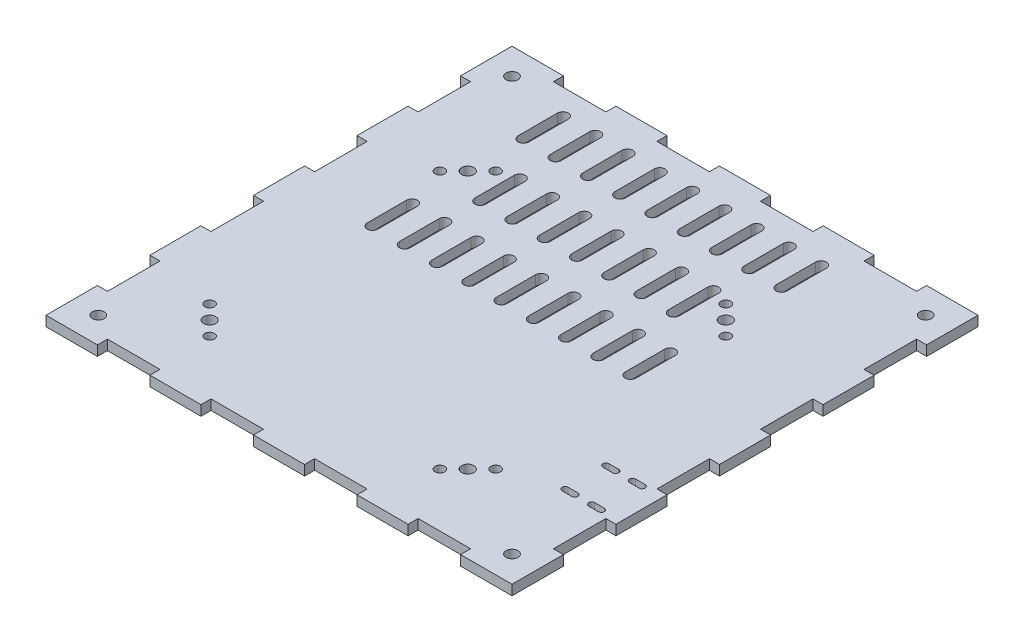
SolidWorks part; units mm, degrees
material "Acrylic (Medium-high impact)"
ref_plane "Front Plane" through (0, 0, 0) normal (0, 0, 1) x (1, 0, 0)
ref_plane "Top Plane" through (0, 0, 0) normal (0, 1, 0) x (1, 0, 0)
ref_plane "Right Plane" through (0, 0, 0) normal (1, 0, 0) x (0, 0, -1)
sketch "Board refrence" plane through (0, 0, 0) normal (0, 1, 0) x (1, 0, 0)
  line L0 (42.5, -17.26) -> (47.5, -17.26)
  line L1 (-40, -40) -> (40, -40)
  line L2 (-40, -40) -> (-40, 40)
  line L3 (-40, 40) -> (40, 40)
  line L4 (40, -40) -> (40, 40)
  line L5 (-40, -40) -> (40, 40) construction
  line L6 (-40, 40) -> (40, -40) construction
  line L7 (-50.8, 46.35) -> (50.8, 46.35)
  line L8 (-50.8, 46.35) -> (-50.8, 40)
  line L9 (-50.8, 40) -> (50.8, 40)
  line L10 (50.8, 46.35) -> (50.8, 40)
  line L11 (42.5, -25.26) -> (47.5, -25.26)
  line L12 (45, -25.26) -> (45, -17.26) construction
  circle A0 centre (-36, 36) radius 1.6
  circle A1 centre (-36, -36) radius 1.6
  circle A2 centre (36, -36) radius 1.6
  circle A3 centre (36, 36) radius 1.6
  point P0 (0, 0)
  point P14 (0, 40)
  point P15 (0, 40)
  point P26 (45, -21.26)
  dimension "D4" = 3.2
  dimension "D1" = 80
  dimension "D2" = 80
  dimension "D3" = 4
  dimension "D5" = 6.35
  dimension "D6" = 101.6
  dimension "D7" = 18.74
  dimension "D8" = 8
  dimension "D9" = 5
  dimension "D10" = 5
sketch "Sketch2" plane through (0, 0, 0) normal (0, 1, 0) x (1, 0, 0)
  line L0 (-40, -40) -> (-40, 40) construction
  line L1 (-56.8, 69.15) -> (66.8, 69.15) construction
  line L2 (-56.8, 69.15) -> (-56.8, -54.45) construction
  line L3 (-56.8, -54.45) -> (66.8, -54.45) construction
  line L4 (66.8, 69.15) -> (66.8, -54.45) construction
  line L6 (40, -40) -> (40, 40) construction
  line L7 (-50.8, 46.35) -> (50.8, 46.35) construction
  line L8 (-60, 72.35) -> (-60, -57.65)
  line L9 (-60, -57.65) -> (70, -57.65)
  line L10 (70, 72.35) -> (70, -57.65)
  line L11 (-60, 72.35) -> (70, 72.35)
  circle A0 centre (-36, 36) radius 1.7
  circle A1 centre (-36, -36) radius 1.7
  circle A2 centre (36, -36) radius 1.7
  circle A3 centre (36, 36) radius 1.7
  point P16 (0, 0)
  dimension "D1" = 3.4
  dimension "D2" = 20
  dimension "D3" = 26
  dimension "D4" = 30
  dimension "D6" = 130
  dimension "D7" = 130
  dimension "D5" = 3.2
extrude "Boss-Extrude1" add sketch "Sketch2" along normal blind 2.8
sketch "Sketch5" plane through (0, 2.8, 0) normal (0, 1, 0) x (1, 0, 0)
  line L0 (32.1109, 39.8891) -> (39.8891, 32.1109) construction
  line L1 (70, -57.65) -> (70, 72.35) construction
  circle A0 centre (39.8891, 32.1109) radius 1.35
  circle A1 centre (32.1109, 39.8891) radius 1.35
  circle A2 centre (32.1109, -39.8891) radius 1.35
  circle A3 centre (39.8891, -32.1109) radius 1.35
  circle A4 centre (-39.8891, -32.1109) radius 1.35
  circle A5 centre (-32.1109, -39.8891) radius 1.35
  circle A6 centre (-32.1109, 39.8891) radius 1.35
  circle A7 centre (-39.8891, 32.1109) radius 1.35
  point P4 (36, 36)
  point P23 (0, 0)
  dimension "D3" = 2.7
  dimension "D1" = 45
  dimension "D2" = 11
extrude "Cut-Extrude2" cut sketch "Sketch5" against normal up to next
sketch "Sketch4" plane through (0, 2.8, 0) normal (0, 1, 0) x (1, 0, 0)
  line L0 (70, 57.9056) -> (70, 43.4611)
  line L1 (70, -57.65) -> (70, 72.35) construction
  line L2 (70, 14.5722) -> (67.2, 14.5722)
  line L3 (67.2, 14.5722) -> (67.2, 29.0167)
  line L4 (67.2, 29.0167) -> (70, 29.0167)
  line L5 (70, 29.0167) -> (70, 14.5722)
  line L6 (70, -14.3167) -> (67.2, -14.3167)
  line L7 (67.2, -14.3167) -> (67.2, 0.1278)
  line L8 (67.2, 0.1278) -> (70, 0.1278)
  line L9 (70, 0.1278) -> (70, -14.3167)
  line L10 (70, 43.4611) -> (67.2, 43.4611)
  line L11 (67.2, 43.4611) -> (67.2, 57.9056)
  line L12 (67.2, 57.9056) -> (70, 57.9056)
  line L13 (70, -43.2056) -> (67.2, -43.2056)
  line L14 (67.2, -43.2056) -> (67.2, -28.7611)
  line L15 (67.2, -28.7611) -> (70, -28.7611)
  line L16 (70, -28.7611) -> (70, -43.2056)
  line L17 (70, 43.4611) -> (70, 14.5722) construction
  line L18 (67.2, -43.2056) -> (67.2, -57.65) construction
  line L19 (-60, -57.65) -> (70, -57.65) construction
  line L20 (67.2, -28.7611) -> (67.2, -14.3167) construction
  line L21 (70, 72.35) -> (-60, 72.35) construction
  line L42 (-60, 72.35) -> (70, -57.65) construction
  line L66 (-45.5556, -57.65) -> (-45.5556, -54.85)
  line L67 (-45.5556, -54.85) -> (-31.1111, -54.85)
  line L68 (-31.1111, -54.85) -> (-31.1111, -57.65)
  line L91 (67.2, 0.1278) -> (67.2, 14.5722) construction
  line L92 (67.2, 29.0167) -> (67.2, 43.4611) construction
  line L93 (67.2, 57.9056) -> (67.2, 72.35) construction
  line L94 (-31.1111, -57.65) -> (-45.5556, -57.65)
  line L95 (-16.6667, -57.65) -> (-16.6667, -54.85)
  line L96 (-16.6667, -54.85) -> (-2.2222, -54.85)
  line L97 (-2.2222, -54.85) -> (-2.2222, -57.65)
  line L103 (-2.2222, -57.65) -> (-16.6667, -57.65)
  line L108 (12.2222, -57.65) -> (12.2222, -54.85)
  line L113 (12.2222, -54.85) -> (26.6667, -54.85)
  line L118 (26.6667, -54.85) -> (26.6667, -57.65)
  line L119 (26.6667, -57.65) -> (12.2222, -57.65)
  line L120 (55.5556, -57.65) -> (41.1111, -57.65)
  line L121 (41.1111, -57.65) -> (41.1111, -54.85)
  line L125 (41.1111, -54.85) -> (55.5556, -54.85)
  line L126 (55.5556, -54.85) -> (55.5556, -57.65)
  line L127 (-60, 57.9056) -> (-57.2, 57.9056)
  line L128 (-57.2, 57.9056) -> (-57.2, 43.4611)
  line L129 (-57.2, 43.4611) -> (-60, 43.4611)
  line L130 (-60, 43.4611) -> (-60, 57.9056)
  line L131 (-60, 29.0167) -> (-57.2, 29.0167)
  line L132 (-57.2, 29.0167) -> (-57.2, 14.5722)
  line L133 (-57.2, 14.5722) -> (-60, 14.5722)
  line L134 (-60, 14.5722) -> (-60, 29.0167)
  line L135 (-60, 0.1278) -> (-57.2, 0.1278)
  line L136 (-57.2, 0.1278) -> (-57.2, -14.3167)
  line L137 (-57.2, -14.3167) -> (-60, -14.3167)
  line L138 (-60, -14.3167) -> (-60, 0.1278)
  line L139 (-60, -43.2056) -> (-60, -28.7611)
  line L140 (-60, -28.7611) -> (-57.2, -28.7611)
  line L141 (-57.2, -28.7611) -> (-57.2, -43.2056)
  line L142 (-57.2, -43.2056) -> (-60, -43.2056)
  line L143 (55.5556, 72.35) -> (55.5556, 69.55)
  line L144 (55.5556, 69.55) -> (41.1111, 69.55)
  line L145 (41.1111, 69.55) -> (41.1111, 72.35)
  line L146 (41.1111, 72.35) -> (55.5556, 72.35)
  line L147 (26.6667, 72.35) -> (26.6667, 69.55)
  line L148 (26.6667, 69.55) -> (12.2222, 69.55)
  line L149 (12.2222, 69.55) -> (12.2222, 72.35)
  line L150 (12.2222, 72.35) -> (26.6667, 72.35)
  line L151 (-2.2222, 72.35) -> (-2.2222, 69.55)
  line L152 (-2.2222, 69.55) -> (-16.6667, 69.55)
  line L153 (-16.6667, 69.55) -> (-16.6667, 72.35)
  line L154 (-16.6667, 72.35) -> (-2.2222, 72.35)
  line L155 (-45.5556, 72.35) -> (-31.1111, 72.35)
  line L156 (-31.1111, 72.35) -> (-31.1111, 69.55)
  line L157 (-31.1111, 69.55) -> (-45.5556, 69.55)
  line L158 (-45.5556, 69.55) -> (-45.5556, 72.35)
  point P27 (5, 7.35)
  point P81 (5, 7.35)
  dimension "D4" = 2.8
  dimension "D1" = 4
  dimension "D2" = 4
extrude "Cut tabs" cut sketch "Sketch4" against normal through all
sketch "Pad reference" plane through (0, 2.8, 0) normal (0, 1, 0) x (1, 0, 0)
  line L2 (-60, -57.65) -> (-45.5556, -57.65) construction
  line L3 (55, 57.35) -> (-45, 57.35) construction
  line L4 (55, 57.35) -> (55, -42.65) construction
  line L5 (55, -42.65) -> (-45, -42.65) construction
  line L7 (-45, 57.35) -> (-45, -42.65) construction
  line L151 (70, -57.65) -> (70, -43.2056) construction
  line L152 (70, 72.35) -> (55.5556, 72.35) construction
  circle A0 centre (-45, 57.35) radius 4
  circle A1 centre (55, 57.35) radius 4
  circle A2 centre (55, -42.65) radius 4
  circle A3 centre (-45, -42.65) radius 4
  point P6 (0, 0)
  dimension "D1" = 8
  dimension "D3" = 15
  dimension "D4" = 15
  dimension "D2" = 15
sketch "Sketch6" plane through (0, 2.8, 0) normal (0, 1, 0) x (1, 0, 0)
  line L0 (64.5, -27.2389) -> (61.8, -27.2389) construction
  line L1 (64.5, -28.0889) -> (61.8, -28.0889)
  line L2 (64.5, -26.3889) -> (61.8, -26.3889)
  line L3 (57.1, -27.2389) -> (54.4, -27.2389) construction
  line L4 (57.1, -28.0889) -> (54.4, -28.0889)
  line L5 (57.1, -26.3889) -> (54.4, -26.3889)
  line L6 (72.5, -21.5389) -> (-49927.5, -21.5389) construction
  line L7 (70, -28.7611) -> (70, -14.3167) construction
  line L8 (57.1, -15.8389) -> (54.4, -15.8389) construction
  line L9 (57.1, -14.9889) -> (54.4, -14.9889)
  line L10 (57.1, -16.6889) -> (54.4, -16.6889)
  line L11 (64.5, -15.8389) -> (61.8, -15.8389) construction
  line L12 (64.5, -14.9889) -> (61.8, -14.9889)
  line L13 (64.5, -16.6889) -> (61.8, -16.6889)
  arc A0 (64.5, -28.0889) -> (64.5, -26.3889) centre (64.5, -27.2389) ccw
  arc A1 (61.8, -26.3889) -> (61.8, -28.0889) centre (61.8, -27.2389) ccw
  arc A2 (57.1, -28.0889) -> (57.1, -26.3889) centre (57.1, -27.2389) ccw
  arc A3 (54.4, -26.3889) -> (54.4, -28.0889) centre (54.4, -27.2389) ccw
  arc A4 (57.1, -14.9889) -> (57.1, -16.6889) centre (57.1, -15.8389) cw
  arc A5 (54.4, -16.6889) -> (54.4, -14.9889) centre (54.4, -15.8389) cw
  arc A6 (64.5, -14.9889) -> (64.5, -16.6889) centre (64.5, -15.8389) cw
  arc A7 (61.8, -16.6889) -> (61.8, -14.9889) centre (61.8, -15.8389) cw
  point P2 (63.15, -27.2389)
  point P7 (55.75, -27.2389)
  point P18 (70, -21.5389)
  point P21 (55.75, -15.8389)
  point P28 (63.15, -15.8389)
  dimension "D3" = 3
  dimension "D1" = 4.4
  dimension "D2" = 1.7
  dimension "D4" = 4.85
  dimension "D5" = 5.5
extrude "Power cord slots" cut sketch "Sketch6" against normal up to next
sketch "Sketch7" plane through (0, 2.8, 0) normal (0, 1, 0) x (1, 0, 0)
  line L0 (-36, 62.55) -> (-36, 51.55) construction
  line L1 (-34.5, 62.55) -> (-34.5, 51.55)
  line L2 (-37.5, 62.55) -> (-37.5, 51.55)
  line L3 (-45.5556, 69.55) -> (-31.1111, 69.55) construction
  line L4 (-37.5, 20.45) -> (-37.5, 9.45)
  line L5 (-28.5, 62.55) -> (-28.5, 51.55)
  line L6 (-25.5, 62.55) -> (-25.5, 51.55)
  line L7 (-27, 62.55) -> (-27, 51.55) construction
  line L8 (-19.5, 62.55) -> (-19.5, 51.55)
  line L9 (-16.5, 62.55) -> (-16.5, 51.55)
  line L10 (-18, 62.55) -> (-18, 51.55) construction
  line L11 (-10.5, 62.55) -> (-10.5, 51.55)
  line L12 (-7.5, 62.55) -> (-7.5, 51.55)
  line L13 (-9, 62.55) -> (-9, 51.55) construction
  line L14 (-1.5, 62.55) -> (-1.5, 51.55)
  line L15 (1.5, 62.55) -> (1.5, 51.55)
  line L16 (0, 62.55) -> (0, 51.55) construction
  line L17 (7.5, 62.55) -> (7.5, 51.55)
  line L18 (10.5, 62.55) -> (10.5, 51.55)
  line L19 (9, 62.55) -> (9, 51.55) construction
  line L20 (16.5, 62.55) -> (16.5, 51.55)
  line L21 (19.5, 62.55) -> (19.5, 51.55)
  line L22 (18, 62.55) -> (18, 51.55) construction
  line L23 (25.5, 62.55) -> (25.5, 51.55)
  line L24 (28.5, 62.55) -> (28.5, 51.55)
  line L25 (27, 62.55) -> (27, 51.55) construction
  line L26 (34.5, 62.55) -> (34.5, 51.55)
  line L27 (37.5, 62.55) -> (37.5, 51.55)
  line L28 (36, 62.55) -> (36, 51.55) construction
  line L32 (-36, 36) -> (-36, 51.55) construction
  line L33 (-36, 36) -> (-36, 20.45) construction
  line L34 (-34.5, 20.45) -> (-34.5, 9.45)
  line L37 (-28.5, 41.5) -> (-28.5, 30.5)
  line L38 (-25.5, 41.5) -> (-25.5, 30.5)
  line L39 (-27, 41.5) -> (-27, 30.5) construction
  line L40 (-19.5, 41.5) -> (-19.5, 30.5)
  line L41 (-16.5, 41.5) -> (-16.5, 30.5)
  line L42 (-18, 41.5) -> (-18, 30.5) construction
  line L43 (-10.5, 41.5) -> (-10.5, 30.5)
  line L44 (-7.5, 41.5) -> (-7.5, 30.5)
  line L45 (-9, 41.5) -> (-9, 30.5) construction
  line L46 (-1.5, 41.5) -> (-1.5, 30.5)
  line L47 (1.5, 41.5) -> (1.5, 30.5)
  line L48 (0, 41.5) -> (0, 30.5) construction
  line L49 (7.5, 41.5) -> (7.5, 30.5)
  line L50 (10.5, 41.5) -> (10.5, 30.5)
  line L51 (9, 41.5) -> (9, 30.5) construction
  line L52 (16.5, 41.5) -> (16.5, 30.5)
  line L53 (19.5, 41.5) -> (19.5, 30.5)
  line L54 (18, 41.5) -> (18, 30.5) construction
  line L55 (25.5, 41.5) -> (25.5, 30.5)
  line L56 (28.5, 41.5) -> (28.5, 30.5)
  line L57 (27, 41.5) -> (27, 30.5) construction
  line L63 (-36, 20.45) -> (-36, 9.45) construction
  line L64 (-28.5, 20.45) -> (-28.5, 9.45)
  line L65 (-25.5, 20.45) -> (-25.5, 9.45)
  line L66 (-27, 20.45) -> (-27, 9.45) construction
  line L67 (-19.5, 20.45) -> (-19.5, 9.45)
  line L68 (-16.5, 20.45) -> (-16.5, 9.45)
  line L69 (-18, 20.45) -> (-18, 9.45) construction
  line L70 (-10.5, 20.45) -> (-10.5, 9.45)
  line L71 (-7.5, 20.45) -> (-7.5, 9.45)
  line L72 (-9, 20.45) -> (-9, 9.45) construction
  line L73 (-1.5, 20.45) -> (-1.5, 9.45)
  line L74 (1.5, 20.45) -> (1.5, 9.45)
  line L75 (0, 20.45) -> (0, 9.45) construction
  line L76 (7.5, 20.45) -> (7.5, 9.45)
  line L77 (10.5, 20.45) -> (10.5, 9.45)
  line L78 (9, 20.45) -> (9, 9.45) construction
  line L79 (16.5, 20.45) -> (16.5, 9.45)
  line L80 (19.5, 20.45) -> (19.5, 9.45)
  line L81 (18, 20.45) -> (18, 9.45) construction
  line L82 (25.5, 20.45) -> (25.5, 9.45)
  line L83 (28.5, 20.45) -> (28.5, 9.45)
  line L84 (27, 20.45) -> (27, 9.45) construction
  line L85 (34.5, 20.45) -> (34.5, 9.45)
  line L86 (37.5, 20.45) -> (37.5, 9.45)
  line L87 (36, 20.45) -> (36, 9.45) construction
  line L88 (34.5, 41.5) -> (34.5, 30.5) [skipped]
  line L89 (37.5, 41.5) -> (37.5, 30.5) [skipped]
  line L90 (-37.5, 41.5) -> (-37.5, 30.5) [skipped]
  line L91 (-34.5, 41.5) -> (-34.5, 30.5) [skipped]
  line L93 (-37.5, 62.55) -> (-28.5, 62.55) construction
  arc A0 (-34.5, 62.55) -> (-37.5, 62.55) centre (-36, 62.55) ccw
  arc A1 (-37.5, 51.55) -> (-34.5, 51.55) centre (-36, 51.55) ccw
  arc A2 (-25.5, 62.55) -> (-28.5, 62.55) centre (-27, 62.55) ccw
  arc A3 (-28.5, 51.55) -> (-25.5, 51.55) centre (-27, 51.55) ccw
  arc A4 (-16.5, 62.55) -> (-19.5, 62.55) centre (-18, 62.55) ccw
  arc A5 (-19.5, 51.55) -> (-16.5, 51.55) centre (-18, 51.55) ccw
  arc A6 (-7.5, 62.55) -> (-10.5, 62.55) centre (-9, 62.55) ccw
  arc A7 (-10.5, 51.55) -> (-7.5, 51.55) centre (-9, 51.55) ccw
  arc A8 (1.5, 62.55) -> (-1.5, 62.55) centre (0, 62.55) ccw
  arc A9 (-1.5, 51.55) -> (1.5, 51.55) centre (0, 51.55) ccw
  arc A10 (10.5, 62.55) -> (7.5, 62.55) centre (9, 62.55) ccw
  arc A11 (7.5, 51.55) -> (10.5, 51.55) centre (9, 51.55) ccw
  arc A12 (19.5, 62.55) -> (16.5, 62.55) centre (18, 62.55) ccw
  arc A13 (16.5, 51.55) -> (19.5, 51.55) centre (18, 51.55) ccw
  arc A14 (28.5, 62.55) -> (25.5, 62.55) centre (27, 62.55) ccw
  arc A15 (25.5, 51.55) -> (28.5, 51.55) centre (27, 51.55) ccw
  arc A16 (37.5, 62.55) -> (34.5, 62.55) centre (36, 62.55) ccw
  arc A17 (34.5, 51.55) -> (37.5, 51.55) centre (36, 51.55) ccw
  arc A20 (-25.5, 41.5) -> (-28.5, 41.5) centre (-27, 41.5) ccw
  arc A21 (-28.5, 30.5) -> (-25.5, 30.5) centre (-27, 30.5) ccw
  arc A22 (-16.5, 41.5) -> (-19.5, 41.5) centre (-18, 41.5) ccw
  arc A23 (-19.5, 30.5) -> (-16.5, 30.5) centre (-18, 30.5) ccw
  arc A24 (-7.5, 41.5) -> (-10.5, 41.5) centre (-9, 41.5) ccw
  arc A25 (-10.5, 30.5) -> (-7.5, 30.5) centre (-9, 30.5) ccw
  arc A26 (1.5, 41.5) -> (-1.5, 41.5) centre (0, 41.5) ccw
  arc A27 (-1.5, 30.5) -> (1.5, 30.5) centre (0, 30.5) ccw
  arc A28 (10.5, 41.5) -> (7.5, 41.5) centre (9, 41.5) ccw
  arc A29 (7.5, 30.5) -> (10.5, 30.5) centre (9, 30.5) ccw
  arc A30 (19.5, 41.5) -> (16.5, 41.5) centre (18, 41.5) ccw
  arc A31 (16.5, 30.5) -> (19.5, 30.5) centre (18, 30.5) ccw
  arc A32 (28.5, 41.5) -> (25.5, 41.5) centre (27, 41.5) ccw
  arc A33 (25.5, 30.5) -> (28.5, 30.5) centre (27, 30.5) ccw
  arc A36 (-34.5, 20.45) -> (-37.5, 20.45) centre (-36, 20.45) ccw
  arc A37 (-37.5, 9.45) -> (-34.5, 9.45) centre (-36, 9.45) ccw
  arc A38 (-25.5, 20.45) -> (-28.5, 20.45) centre (-27, 20.45) ccw
  arc A39 (-28.5, 9.45) -> (-25.5, 9.45) centre (-27, 9.45) ccw
  arc A40 (-16.5, 20.45) -> (-19.5, 20.45) centre (-18, 20.45) ccw
  arc A41 (-19.5, 9.45) -> (-16.5, 9.45) centre (-18, 9.45) ccw
  arc A42 (-7.5, 20.45) -> (-10.5, 20.45) centre (-9, 20.45) ccw
  arc A43 (-10.5, 9.45) -> (-7.5, 9.45) centre (-9, 9.45) ccw
  arc A44 (1.5, 20.45) -> (-1.5, 20.45) centre (0, 20.45) ccw
  arc A45 (-1.5, 9.45) -> (1.5, 9.45) centre (0, 9.45) ccw
  arc A46 (10.5, 20.45) -> (7.5, 20.45) centre (9, 20.45) ccw
  arc A47 (7.5, 9.45) -> (10.5, 9.45) centre (9, 9.45) ccw
  arc A48 (19.5, 20.45) -> (16.5, 20.45) centre (18, 20.45) ccw
  arc A49 (16.5, 9.45) -> (19.5, 9.45) centre (18, 9.45) ccw
  arc A50 (28.5, 20.45) -> (25.5, 20.45) centre (27, 20.45) ccw
  arc A51 (25.5, 9.45) -> (28.5, 9.45) centre (27, 9.45) ccw
  arc A52 (37.5, 20.45) -> (34.5, 20.45) centre (36, 20.45) ccw
  arc A53 (34.5, 9.45) -> (37.5, 9.45) centre (36, 9.45) ccw
  arc A54 (37.5, 41.5) -> (34.5, 41.5) centre (36, 41.5) ccw [skipped]
  arc A55 (34.5, 30.5) -> (37.5, 30.5) centre (36, 30.5) ccw [skipped]
  arc A56 (-34.5, 41.5) -> (-37.5, 41.5) centre (-36, 41.5) ccw [skipped]
  arc A57 (-37.5, 30.5) -> (-34.5, 30.5) centre (-36, 30.5) ccw [skipped]
  point P2 (-36, 57.05)
  point P10 (-36, 11.7989)
  point P12 (-37.5, 57.05)
  point P14 (0, 0)
  point P16 (-27, 57.05)
  point P23 (-18, 57.05)
  point P30 (-9, 57.05)
  point P37 (0, 57.05)
  point P44 (9, 57.05)
  point P51 (18, 57.05)
  point P58 (27, 57.05)
  point P65 (36, 57.05)
  point P70 (-33.95, 20.45)
  point P71 (-34.5, 9.55)
  point P73 (0, 0)
  point P74 (46.1448, 10.4416)
  point P75 (0, 0)
  point P76 (-36, 9.55)
  point P81 (-36, 20.45)
  point P82 (0, 0)
  point P83 (36, 9.55)
  point P86 (-27, 36)
  point P93 (-18, 36)
  point P100 (-9, 36)
  point P107 (0, 36)
  point P114 (9, 36)
  point P121 (18, 36)
  point P128 (27, 36)
  point P140 (-36, 14.95)
  point P149 (-27, 14.95)
  point P156 (-18, 14.95)
  point P163 (-9, 14.95)
  point P170 (0, 14.95)
  point P177 (9, 14.95)
  point P184 (18, 14.95)
  point P191 (27, 14.95)
  point P198 (36, 14.95)
  dimension "D1" = 7
  dimension "D2" = 11
  dimension "D4" = 3
  dimension "D7" = 9
  dimension "D5" = 9
  dimension "D6" = 3
extrude "Cooling slots" cut sketch "Sketch7" against normal up to next (2.8 mm away)
sketch "Sketch8" plane through (0, 2.8, 0) normal (0, 1, 0) x (1, 0, 0)
  line L1 (-60, 72.35) -> (70, 72.35) construction
  line L2 (-60, 72.35) -> (-60, -57.65) construction
  line L3 (-60, -57.65) -> (70, -57.65) construction
  line L4 (70, 72.35) -> (70, -57.65) construction
  line L72 (-52.7, 65.05) -> (-52.7, -50.35) construction
  line L73 (-52.7, -50.35) -> (62.7, -50.35) construction
  line L74 (62.7, 65.05) -> (62.7, -50.35) construction
  line L75 (-52.7, 65.05) -> (62.7, 65.05) construction
  circle A0 centre (-52.7, 65.05) radius 1.65
  circle A1 centre (62.7, 65.05) radius 1.65
  circle A2 centre (62.7, -50.35) radius 1.65
  circle A3 centre (-52.7, -50.35) radius 1.65
  dimension "D1" = 3.3
  dimension "D2" = 7.3
extrude "Cornerpiece holes" cut sketch "Sketch8" against normal up to next
other "Tolerance" flip direction yes face at (41.1111, 1.4, -70.95) face at (12.2222, 1.4, -70.95) face at (-16.6667, 1.4, -70.95) face at (-45.5556, 1.4, -70.95) face at (26.6667, 1.4, -70.95) face at (55.5556, 1.4, -70.95) face at (-2.2222, 1.4, -70.95) face at (-31.1111, 1.4, -70.95) face at (-58.6, 1.4, -43.4611) face at (-58.6, 1.4, -57.9056) face at (-58.6, 1.4, -14.5722) face at (-58.6, 1.4, -29.0167) face at (-58.6, 1.4, -0.1278) face at (-58.6, 1.4, 14.3167) face at (-58.6, 1.4, 43.2056) face at (-58.6, 1.4, 28.7611) face at (-31.1111, 1.4, 56.25) face at (-45.5556, 1.4, 56.25) face at (-16.6667, 1.4, 56.25) face at (-2.2222, 1.4, 56.25) face at (12.2222, 1.4, 56.25) face at (26.6667, 1.4, 56.25) face at (55.5556, 1.4, 56.25) face at (41.1111, 1.4, 56.25) face at (68.6, 1.4, 28.7611) face at (68.6, 1.4, 43.2056) face at (68.6, 1.4, 14.3167) face at (68.6, 1.4, -0.1278) face at (68.6, 1.4, -14.5722) face at (68.6, 1.4, -29.0167) face at (68.6, 1.4, -57.9056) face at (68.6, 1.4, -43.4611) offset 0.1 parameters "D1"=0.1
equation "\"D5@Board refrence\" =  ( 1 / 4 )  * 1in"
equation "\"D6@Board refrence\" = 4in"
equation "\"slot_depth\"= 2.8mm"
equation "\"slot_width_tolerance\"= 0.0mm"
equation "\"D4@Sketch4\"=\"slot_depth\""
equation "\"D2@Sketch8\"=4.50+2.8"
